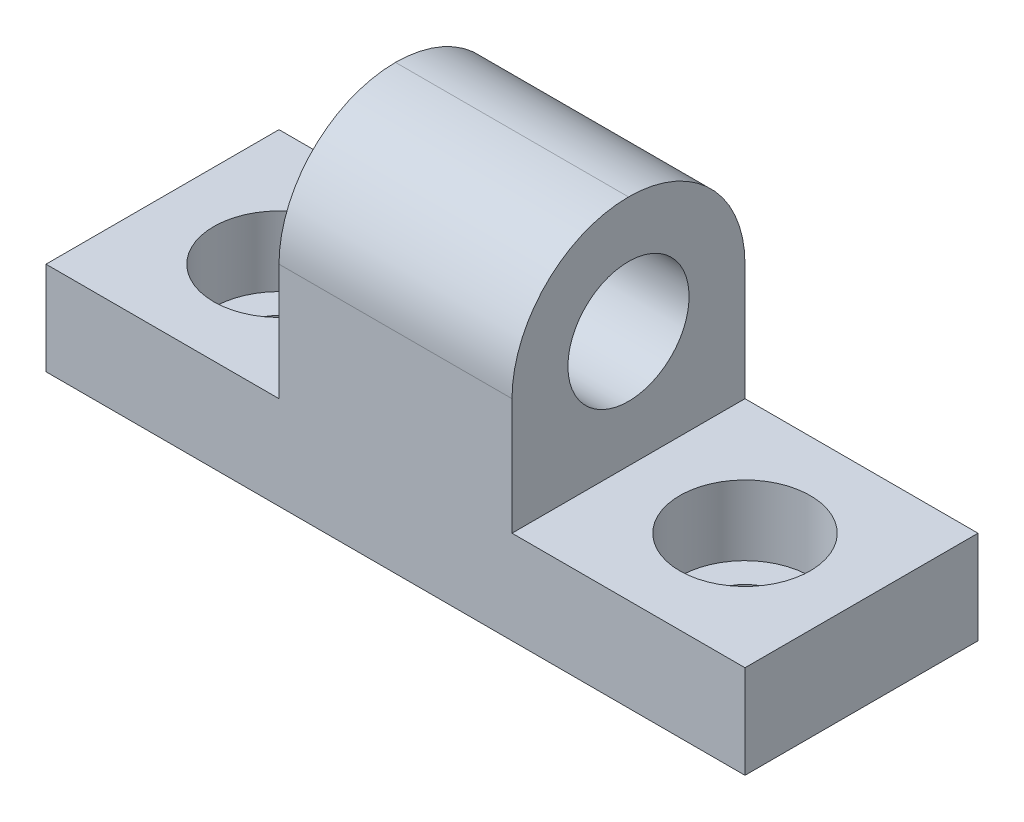
SolidWorks part; units mm, degrees
ref_plane "Alzado" through (0, 0, 0) normal (0, 0, 1) x (1, 0, 0)
ref_plane "Planta" through (0, 0, 0) normal (0, 1, 0) x (1, 0, 0)
ref_plane "Vista lateral" through (0, 0, 0) normal (1, 0, 0) x (0, 0, -1)
sketch "Croquis1" plane through (0, 0, 0) normal (0, 1, 0) x (1, 0, 0)
  line L0 (15, 0) -> (15, 10) construction
  line L1 (0, 0) -> (30, 0)
  line L2 (0, 0) -> (0, 10)
  line L3 (0, 10) -> (30, 10)
  line L4 (30, 0) -> (30, 10)
  line L5 (5, 5) -> (15, 5) construction
  line L6 (15, 5) -> (25, 5) construction
  circle A0 centre (5, 5) radius 1.55
  circle A1 centre (25, 5) radius 1.55
  dimension "D3" = 10
  dimension "D4" = 3.1
  dimension "D1" = 30
  dimension "D2" = 10
extrude "Saliente-Extruir1" add sketch "Croquis1" along normal blind 4
sketch "Croquis2" plane through (0, 4, 0) normal (0, 1, 0) x (1, 0, 0)
  circle A0 centre (5, 5) radius 2.8
  circle A1 centre (25, 5) radius 2.8
  dimension "D1" = 5.6
extrude "Cortar-Extruir1" cut sketch "Croquis2" against normal blind 3
sketch "Croquis3" plane through (0, 4, 0) normal (0, 1, 0) x (1, 0, 0)
  line L0 (0, 0) -> (30, 0) construction
  line L1 (10, 0) -> (20, 0)
  line L2 (10, 0) -> (10, 10)
  line L3 (10, 10) -> (20, 10)
  line L4 (20, 0) -> (20, 10)
  line L5 (30, 10) -> (0, 10) construction
  line L6 (15, 10) -> (15, 0) construction
  dimension "D1" = 10
extrude "Saliente-Extruir2" add sketch "Croquis3" along normal blind 10
sketch "Croquis4" plane through (10, 0, 0) normal (-1, 0, 0) x (0, 0, 1)
  line L0 (-10, 14) -> (0, 4) construction
  circle A0 centre (-5, 9) radius 2.6
  dimension "D1" = 5.2
extrude "Cortar-Extruir2" cut sketch "Croquis4" against normal blind 10
fillet "Redondeo3" radius 5 2 edges at (15, 14, 0) (15, 14, -10)
